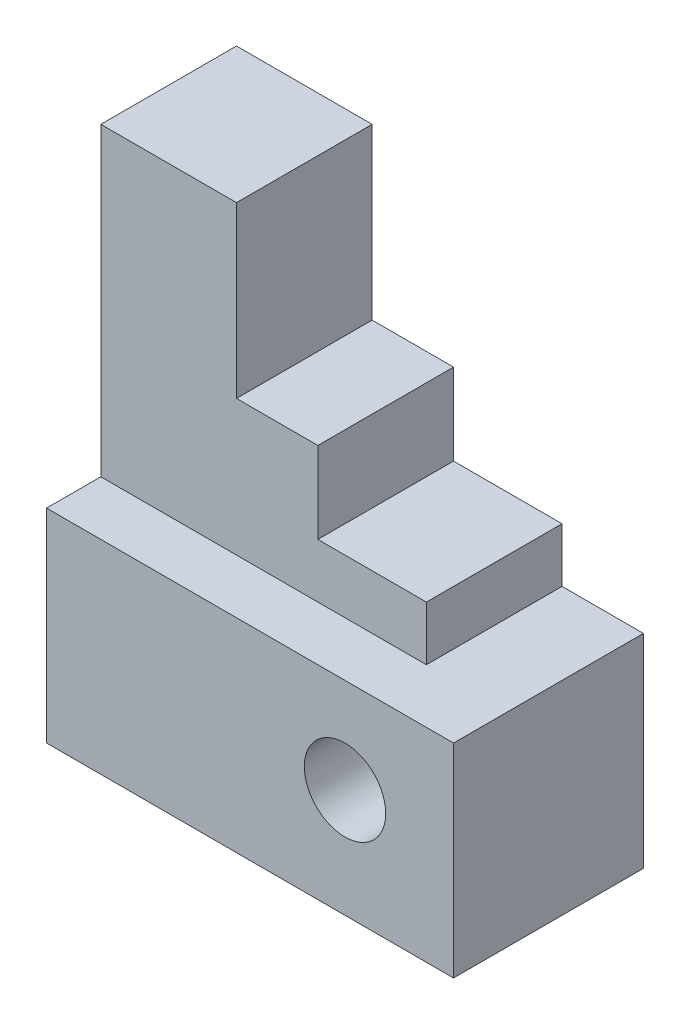
SolidWorks part; units mm, degrees
ref_plane "Front Plane" through (0, 0, 0) normal (0, 0, 1) x (1, 0, 0)
ref_plane "Top Plane" through (0, 0, 0) normal (0, 1, 0) x (1, 0, 0)
ref_plane "Right Plane" through (0, 0, 0) normal (1, 0, 0) x (0, 0, -1)
sketch "Sketch1" plane through (0, 0, 0) normal (0, 1, 0) x (1, 0, 0)
  line L1 (-30, 14) -> (30, 14)
  line L2 (-30, 14) -> (-30, -14)
  line L3 (-30, -14) -> (30, -14)
  line L4 (30, 14) -> (30, -14)
  line L5 (-30, 14) -> (30, -14) construction
  line L6 (-30, -14) -> (30, 14) construction
  point P0 (0, 0)
  dimension "D1" = 28
  dimension "D2" = 60
extrude "Boss-Extrude1" add sketch "Sketch1" along normal blind 30
sketch "Sketch2" plane through (0, 30, 0) normal (0, 1, 0) x (1, 0, 0)
  line L0 (30, -14) -> (30, 14) construction
  line L1 (-30, 14) -> (18, 14)
  line L2 (-30, 14) -> (-30, -6)
  line L3 (-30, -6) -> (18, -6)
  line L4 (18, 14) -> (18, -6)
  line L5 (-30, 14) -> (2, 14)
  line L6 (-30, 14) -> (-30, -6)
  line L7 (-30, -6) -> (2, -6)
  line L8 (2, 14) -> (2, -6)
  line L9 (-30, 14) -> (-10, 14)
  line L10 (-30, 14) -> (-30, -6)
  line L11 (-30, -6) -> (-10, -6)
  line L12 (-10, 14) -> (-10, -6)
  line M3 (-30, 14) -> (-30, -14)
  dimension "D1" = 20
  dimension "D2" = 12
  dimension "D3" = 20
  dimension "D4" = 12
extrude "Boss-Extrude2" add sketch "Sketch2" along normal blind 8 contours L2 L3 L4 L1
extrude "Boss-Extrude3" add sketch "Sketch2<3>" along normal blind 20 contours L1 L12 L7 L8 | L12 L5 L3 M3 region at (-20, 30, -4) region at (-4, 30, -4)
sketch "Sketch2<3>" plane through (0, 30, 0) normal (0, 1, 0) x (1, 0, 0) same geometry as "Sketch2"
extrude "Boss-Extrude4" add sketch "Sketch2<4>" along normal blind 45 contours L12 L5 L3 M3 region at (-20, 30, -4)
sketch "Sketch2<4>" plane through (0, 30, 0) normal (0, 1, 0) x (1, 0, 0) same geometry as "Sketch2"
sketch "Sketch4" plane through (0, 0, 14) normal (0, 0, 1) x (1, 0, 0)
  line L0 (30, 30) -> (30, 0) construction
  line L1 (-30, 0) -> (30, 0) construction
  circle A0 centre (14, 16) radius 6
  dimension "D1" = 12
  dimension "D2" = 16
  dimension "D3" = 16
extrude "Cut-Extrude1" cut sketch "Sketch4" against normal through all
